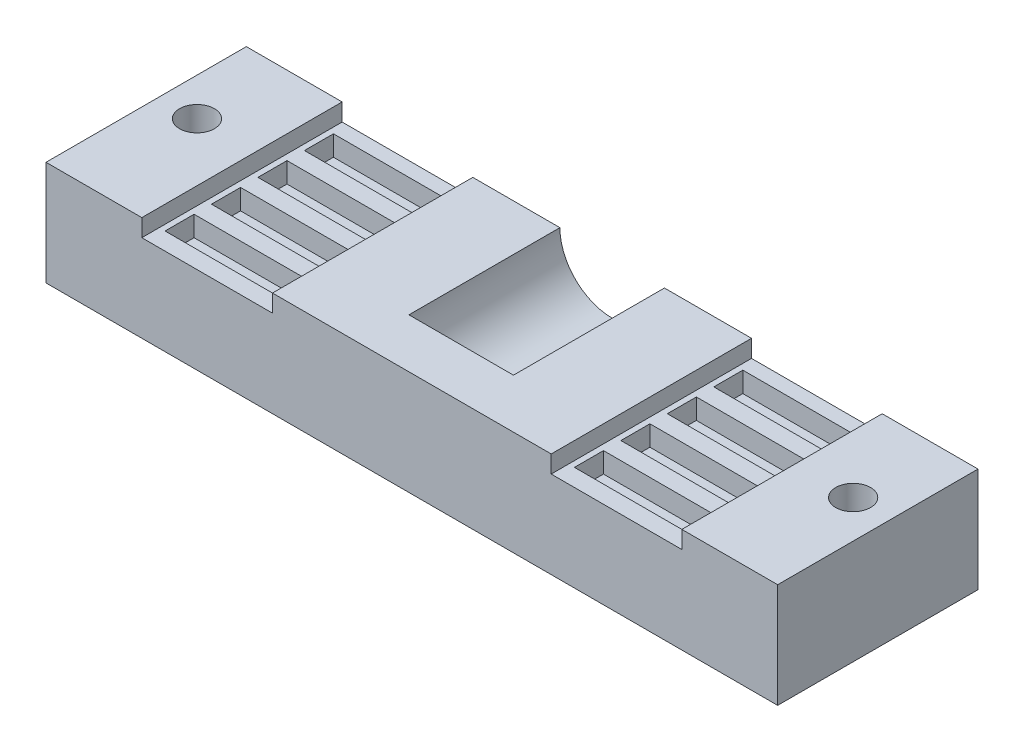
SolidWorks part; units mm, degrees
ref_plane "Alzado" through (0, 0, 0) normal (0, 0, 1) x (1, 0, 0)
ref_plane "Planta" through (0, 0, 0) normal (0, 1, 0) x (1, 0, 0)
ref_plane "Vista lateral" through (0, 0, 0) normal (1, 0, 0) x (0, 0, -1)
sketch "Croquis1" plane through (0, 0, 0) normal (0, 0, 1) x (1, 0, 0)
  line L0 (0, 0) -> (0, 18)
  line L1 (0, 18) -> (16.5, 18)
  line L2 (16.5, 18) -> (16.5, 15)
  line L3 (16.5, 15) -> (39, 15)
  line L4 (39, 15) -> (39, 18)
  line L5 (39, 18) -> (87, 18)
  line L6 (87, 18) -> (87, 15)
  line L7 (87, 15) -> (109.5, 15)
  line L8 (109.5, 15) -> (109.5, 18)
  line L9 (109.5, 18) -> (126, 18)
  line L10 (126, 18) -> (126, 0)
  line L11 (126, 0) -> (0, 0)
  dimension "D1" = 18
  dimension "D2" = 3
  dimension "D3" = 22.5
  dimension "D4" = 22.5
  dimension "D5" = 16.5
  dimension "D6" = 16.5
  dimension "D7" = 126
  dimension "D8" = 48
extrude "Saliente-Extruir1" add sketch "Croquis1" along normal blind 34.5
sketch "Croquis2" plane through (0, 0, 0) normal (0, 0, -1) x (-1, 0, 0)
  line L0 (-87, 18) -> (-39, 18) construction
  circle A0 centre (-63, 18) radius 9
extrude "Cortar-Extruir1" cut sketch "Croquis2" against normal blind 26
sketch "Croquis3" plane through (0, 15, 0) normal (0, 1, 0) x (1, 0, 0)
  line L0 (17.5, -31.5) -> (38, -31.5)
  line L1 (38, -31.5) -> (38, -26.5)
  line L2 (38, -26.5) -> (17.5, -26.5)
  line L3 (17.5, -26.5) -> (17.5, -31.5)
  line L4 (39, -34.5) -> (16.5, -34.5) construction
  line L5 (16.5, -34.5) -> (16.5, 0) construction
  line L7 (27.5, -31.5) -> (38, -31.5)
  line L9 (38, -26.5) -> (27.5, -26.5)
  line L11 (27.5, -23.5) -> (38, -23.5)
  line L13 (38, -18.5) -> (27.5, -18.5)
  line L15 (27.5, -15.5) -> (38, -15.5)
  line L17 (38, -10.5) -> (27.5, -10.5)
  line L19 (27.5, -7.5) -> (38, -7.5)
  line L21 (38, -2.5) -> (27.5, -2.5)
  line L22 (17.5, -18.5) -> (17.5, -23.5)
  line L23 (17.5, -23.5) -> (38, -23.5)
  line L24 (38, -23.5) -> (38, -18.5)
  line L25 (38, -18.5) -> (17.5, -18.5)
  line L26 (17.5, -10.5) -> (17.5, -15.5)
  line L27 (17.5, -15.5) -> (38, -15.5)
  line L28 (38, -15.5) -> (38, -10.5)
  line L29 (38, -10.5) -> (17.5, -10.5)
  line L30 (17.5, -2.5) -> (17.5, -7.5)
  line L31 (17.5, -7.5) -> (38, -7.5)
  line L32 (38, -7.5) -> (38, -2.5)
  line L33 (38, -2.5) -> (17.5, -2.5)
  line L34 (48, -7.5) -> (48, -2.5) [skipped]
  line L35 (48, -15.5) -> (48, -10.5) [skipped]
  line L36 (48, -23.5) -> (48, -18.5) [skipped]
  line L37 (48, -31.5) -> (48, -26.5) [skipped]
  line L38 (27.5, -26.5) -> (27.5, -31.5) [skipped]
  line L39 (27.5, -18.5) -> (27.5, -23.5) [skipped]
  line L40 (27.5, -10.5) -> (27.5, -15.5) [skipped]
  line L41 (27.5, -2.5) -> (27.5, -7.5) [skipped]
  line L43 (63, -34.5) -> (63, 2.3788) construction
  line L44 (87, -34.5) -> (39, -34.5) construction
  line L45 (88, -26.5) -> (108.5, -26.5)
  line L46 (88, -31.5) -> (88, -26.5)
  line L47 (108.5, -31.5) -> (88, -31.5)
  line L48 (108.5, -26.5) -> (108.5, -31.5)
  line L49 (88, -18.5) -> (108.5, -18.5)
  line L50 (88, -23.5) -> (88, -18.5)
  line L51 (108.5, -23.5) -> (88, -23.5)
  line L52 (108.5, -18.5) -> (108.5, -23.5)
  line L53 (88, -10.5) -> (108.5, -10.5)
  line L54 (88, -15.5) -> (88, -10.5)
  line L55 (108.5, -15.5) -> (88, -15.5)
  line L56 (108.5, -10.5) -> (108.5, -15.5)
  line L57 (88, -2.5) -> (108.5, -2.5)
  line L58 (88, -7.5) -> (88, -2.5)
  line L59 (108.5, -7.5) -> (88, -7.5)
  line L60 (108.5, -2.5) -> (108.5, -7.5)
  dimension "D1" = 20.5
  dimension "D2" = 5
  dimension "D3" = 3
  dimension "D4" = 1
  dimension "D5" = 4
  dimension "D6" = 2
extrude "Cortar-Extruir2" cut sketch "Croquis3" against normal blind 3.5 contours L2 L3 L0 L1 | L13 L25 L22 L23 L11 L24 | L17 L29 L26 L27 L15 L28 | L21 L33 L30 L31 L19 L32 | L48 L45 L46 L47 | L52 L49 L50 L51 | L56 L53 L54 L55 | L60 L57 L58 L59 region at (22.5, 15, 29) region at (32.75, 15, 29) region at (32.75, 15, 21) region at (22.5, 15, 21) region at (32.75, 15, 13) region at (22.5, 15, 13) region at (32.75, 15, 5) region at (22.5, 15, 5) region at (98.25, 15, 29) region at (98.25, 15, 21) region at (98.25, 15, 13) region at (98.25, 15, 5)
sketch "Croquis4" plane through (0, 18, 0) normal (0, 1, 0) x (1, 0, 0)
  line L0 (6.5, -15) -> (0, -15) construction
  line L2 (6.5, -15) -> (6.5, 0) construction
  line L5 (16.5, 0) -> (0, 0) construction
  line L6 (0, -34.5) -> (0, 0) construction
  circle A0 centre (6.5, -15) radius 3
  dimension "D1" = 15
extrude "Cortar-Extruir3" cut sketch "Croquis4" against normal through all
ref_plane "Plano1" through (63, 0, 0) normal (-1, 0, 0) x (0, 0, 1)
mirror "Simetría1" about plane through (63, 0, 0) normal (-1, 0, 0) of "Cortar-Extruir3"
